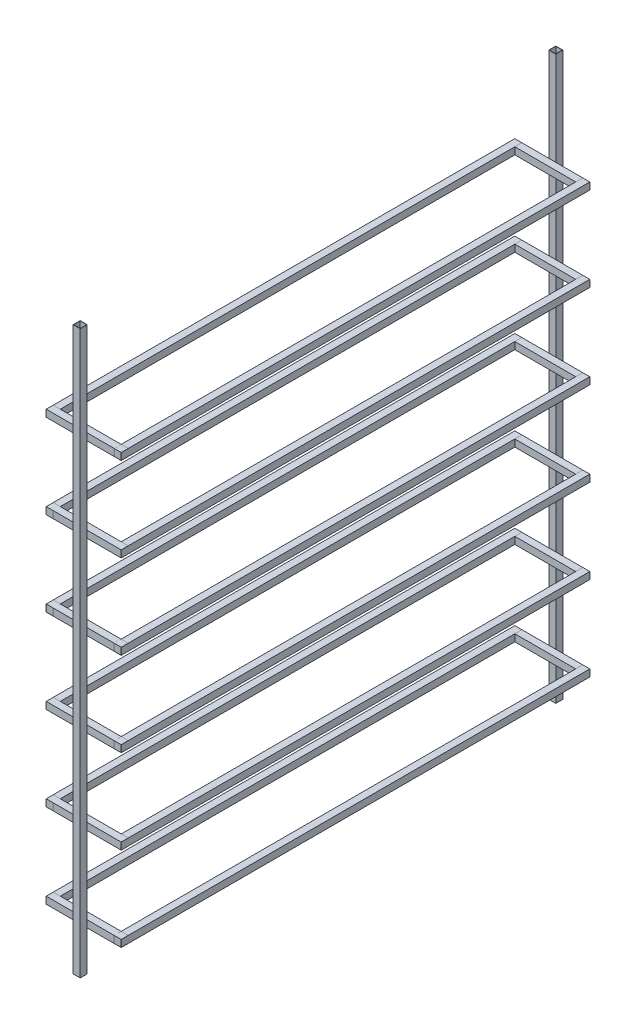
SolidWorks part; units mm, degrees
ref_plane "Alzado" through (0, 0, 0) normal (0, 0, 1) x (1, 0, 0)
ref_plane "Planta" through (0, 0, 0) normal (0, 1, 0) x (1, 0, 0)
ref_plane "Vista lateral" through (0, 0, 0) normal (1, 0, 0) x (0, 0, -1)
sketch "Croquis1" plane through (0, 0, 0) normal (0, 1, 0) x (1, 0, 0)
  line L1 (15, -15) -> (-15, -15)
  line L2 (15, -15) -> (15, 15)
  line L3 (15, 15) -> (-15, 15)
  line L4 (-15, -15) -> (-15, 15)
  line L5 (15, -15) -> (-15, 15) construction
  line L6 (15, 15) -> (-15, -15) construction
  line L7 (0, 0) -> (0, 2030) construction
  line L8 (15, 2015) -> (-15, 2015)
  line L9 (15, 2015) -> (15, 2045)
  line L10 (15, 2045) -> (-15, 2045)
  line L11 (-15, 2015) -> (-15, 2045)
  line L12 (15, 2015) -> (-15, 2045) construction
  line L13 (15, 2045) -> (-15, 2015) construction
  circle A0 centre (0, 0) radius 21.2132 construction
  point P0 (0, 0)
  dimension "D1" = 30
  dimension "D2" = 2030
  dimension "D3" = 30
extrude "Extruir-Lámina1" add sketch "Croquis1" along normal blind 2400 thin thin type one direction reverse wall 1
sketch "Croquis6" plane through (0, 0, 0) normal (1, 0, 0) x (0, 0, -1)
  line L0 (-15, 0) -> (15, 0) construction
  line L1 (15, 170) -> (45, 170)
  line L2 (15, 170) -> (15, 200)
  line L3 (15, 200) -> (45, 200)
  line L4 (45, 170) -> (45, 200)
  line L5 (15, 2400) -> (15, 0) construction
  line L7 (1015, 0) -> (1015, 460) construction
  line L9 (1985, 170) -> (1985, 200)
  line L10 (2015, 200) -> (1985, 200)
  line L11 (2015, 170) -> (2015, 200)
  line L12 (2015, 170) -> (1985, 170)
  dimension "D1" = 170
  dimension "D2" = 1000
extrude "Extruir-Lámina4" add sketch "Croquis6" along normal mid plane 320 separate body thin thin type one direction reverse wall 1
pattern_linear "MatrizL7" count 6 spacing 360 along (0, 1, 0) of bodies 116 110
sketch "Croquis7" plane through (0, 0, -15) normal (0, 0, 1) x (1, 0, 0)
  line L0 (0, 0) -> (0, 2400) construction
  line L1 (160, 170) -> (130, 170)
  line L2 (160, 170) -> (160, 200)
  line L3 (160, 200) -> (130, 200)
  line L4 (130, 170) -> (130, 200)
  line L5 (-15, 2400) -> (15, 2400) construction
  line L6 (-130, 170) -> (-130, 200)
  line L7 (-160, 200) -> (-130, 200)
  line L8 (-160, 170) -> (-160, 200)
  line L9 (-160, 170) -> (-130, 170)
  dimension "D1" = 30
extrude "Extruir-Lámina5" add sketch "Croquis7" against normal up to surface (2000 mm away) separate body thin up to face at (0, 185, -2015) thin type one direction reverse wall 1
pattern_linear "MatrizL9" count 6 spacing 360 along (0, 1, 0) of bodies 134 122 123
